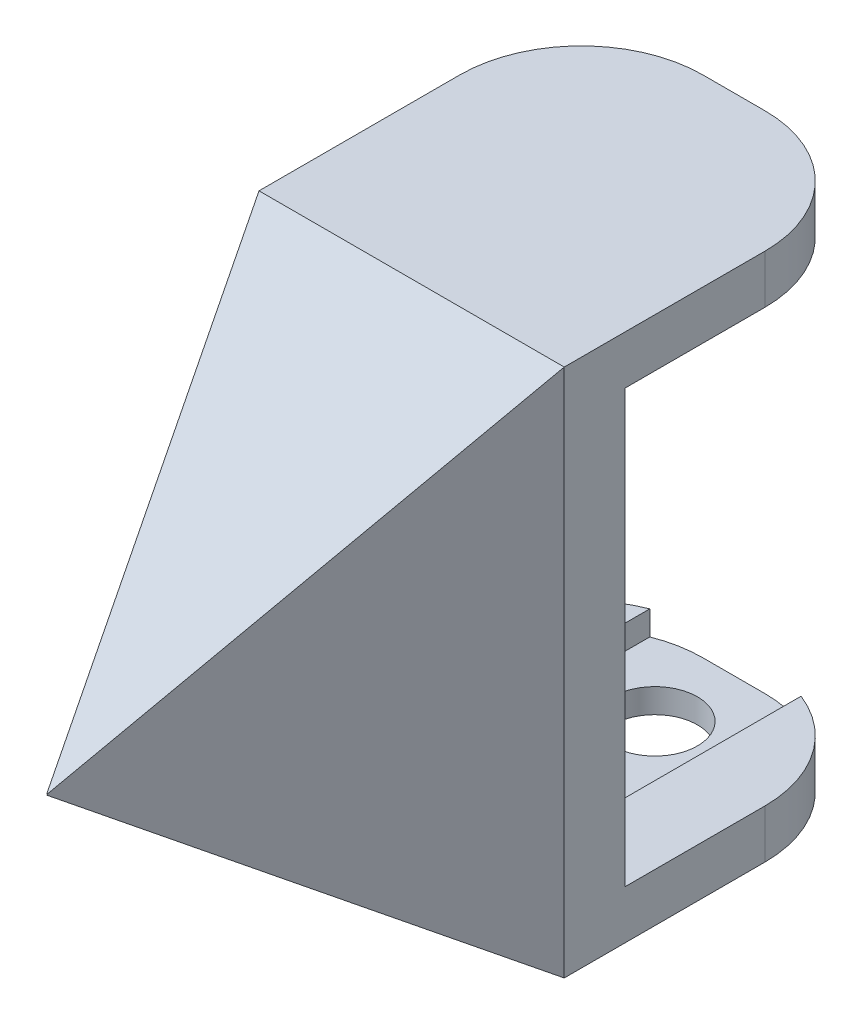
SolidWorks part; units mm, degrees
ref_plane "Front Plane" through (0, 0, 0) normal (0, 0, 1) x (1, 0, 0)
ref_plane "Top Plane" through (0, 0, 0) normal (0, 1, 0) x (1, 0, 0)
ref_plane "Right Plane" through (0, 0, 0) normal (1, 0, 0) x (0, 0, -1)
sketch "Sketch4" plane through (0, 0, 0) normal (0, 0, 1) x (1, 0, 0)
  line L1 (-6.23, -9.975) -> (6.23, -9.975)
  line L2 (-6.23, -9.975) -> (-6.23, 7.275)
  line L3 (-6.23, 7.275) -> (6.23, 7.275)
  line L4 (6.23, -9.975) -> (6.23, 7.275)
  point P4 (0, 7.275)
  dimension "D1" = 12.46
  dimension "D2" = 17.25
  dimension "D3" = 9.975
extrude "Boss-Extrude3" add sketch "Sketch4" along normal blind 6
sketch "Sketch8" plane through (0, -9.975, 0) normal (0, -1, 0) x (-1, 0, 0)
  circle A0 centre (0, -23.55) radius 12.5468
  circle A1 centre (0, -23.55) radius 11.15
  dimension "D1" = 22.3
  dimension "D2" = 23.55
extrude "Boss-Extrude6" add sketch "Sketch8" along normal blind 7.3 and the other way up to surface (17.25 mm away) other way up to face at (0, 7.275, 3)
sketch "Sketch5" plane through (0, 7.275, 0) normal (0, 1, 0) x (1, 0, 0)
  line L8 (12.5468, -23.55) -> (12.5468, 0)
  line L9 (12.5468, 0) -> (6.23, 0)
  line L10 (-12.5468, -23.55) -> (-12.5468, 0)
  line L11 (-12.5468, 0) -> (-6.23, 0)
  line L12 (-6.23, 0) -> (-6.23, -29.7)
  line L14 (6.23, -29.7) -> (6.23, 0)
  line L15 (-6.23, -29.7) -> (6.23, -29.7)
  line L16 (6.23, -6) -> (-6.23, -6) construction
  circle A0 centre (0, -23.55) radius 12.5468 construction
  arc A1 (-12.5468, -23.55) -> (12.5468, -23.55) centre (0, -23.55) ccw
  dimension "D1" = 23.7
  dimension "D2" = 23.55
extrude "Boss-Extrude4" add sketch "Sketch5" against normal up to surface (17.25 mm away) up to face at (0, -9.975, 3)
sketch "Sketch6" plane through (0, 7.275, 0) normal (0, 1, 0) x (1, 0, 0)
  line L0 (6.23, -6) -> (-6.23, -6) construction
  line L3 (6.23, -29.7) -> (-6.23, -29.7) construction
  circle A0 centre (0, -3.5) radius 2
  circle A1 centre (0, -32.2) radius 2
  dimension "D1" = 4
  dimension "D3" = 4
  dimension "D2" = 2.5
  dimension "D4" = 2.5
extrude "Cut-Extrude1" cut sketch "Sketch6" against normal blind 5
chamfer "Chamfer1" distance 0.5 angle 60 2 edges at (0, 7.275, 5.5) (0, 7.275, 34.2) first distance on face at (0, 7.275, 5.5)
sketch "Sketch10" plane through (0, 7.275, 0) normal (0, 1, 0) x (1, 0, 0)
  line L1 (-6.23, -6) -> (6.23, -6)
  line L2 (-6.23, -6) -> (-6.23, -29.7)
  line L3 (-6.23, -29.7) -> (6.23, -29.7)
  line L4 (6.23, -6) -> (6.23, -29.7)
extrude "Cut-Extrude3" cut sketch "Sketch10" against normal up to surface (17.25 mm away) up to face at (0, -9.975, 10.3399)
ref_plane "Plane1" through (0, 0, 36.0968) normal (0, 0, 1) x (1, 0, 0)
sketch "Sketch11" plane through (0, 0, 36.0968) normal (0, 0, 1) x (1, 0, 0)
  line L0 (-11.15, -9.975) -> (11.15, -9.975) construction
  line L1 (-2.5, -6.975) -> (2.5, -6.975)
  line L2 (-2.5, -6.975) -> (-2.5, -9.975)
  line L3 (-2.5, -9.975) -> (2.5, -9.975)
  line L4 (2.5, -6.975) -> (2.5, -9.975)
  point P4 (0, -6.975)
  dimension "D1" = 0
  dimension "D2" = 5
  dimension "D3" = 3
extrude "Cut-Extrude4" cut sketch "Sketch11" against normal up to next
sketch "Sketch13" plane through (0, -17.275, 0) normal (0, -1, 0) x (1, 0, 0)
  line L0 (-12.5468, 23.55) -> (-12.5468, 0)
  line L1 (-12.5468, 0) -> (12.5468, 0)
  line L2 (12.5468, 0) -> (12.5468, 23.55)
  arc A0 (-12.5468, 23.55) -> (12.5468, 23.55) centre (0, 23.55) ccw
  point P3 (0, 0)
extrude "Boss-Extrude7" add sketch "Sketch13" against normal up to surface (7.3 mm away) up to face at (0, -9.975, 10.3399)
sketch "Sketch15" plane through (0, 7.275, 0) normal (0, 1, 0) x (1, 0, 0)
  line L0 (-12.5468, 0) -> (12.5468, 0)
  line L1 (12.5468, 0) -> (12.5468, -23.55)
  line L2 (-12.5468, 0) -> (-12.5468, -23.55)
  line L3 (6.23, -6) -> (6.23, -29.7) construction
  line L4 (-6.23, -0.8) -> (6.23, -0.8)
  line L5 (-6.23, -0.8) -> (-6.23, -33.5)
  line L6 (-5.23, -34.5) -> (5.23, -34.5)
  line L7 (6.23, -0.8) -> (6.23, -33.5)
  arc A0 (-12.5468, -23.55) -> (12.5468, -23.55) centre (0, -23.55) ccw
  circle A1 centre (0, -3.5) radius 2 construction
  arc A2 (5.23, -34.5) -> (6.23, -33.5) centre (5.23, -33.5) ccw
  arc A3 (-6.23, -33.5) -> (-5.23, -34.5) centre (-5.23, -33.5) ccw
  point P15 (0, -0.8)
  dimension "D1" = 0.8
  dimension "D3" = 1
  dimension "D2" = 2.7
  dimension "D4" = 0
  dimension "D5" = 34.5
extrude "Boss-Extrude9" add sketch "Sketch15" along normal blind 10
sketch "Sketch17" plane through (-12.5468, 4.7282, 0) normal (1, 0, 0) x (0, -1, 0)
  line L0 (26.4782, 26.5) -> (26.4782, 0)
  line L1 (26.4782, 0) -> (-17.0218, 0)
  line L2 (-17.0218, 0) -> (-17.0218, 26.5)
  line L3 (-17.0218, 26.5) -> (-13.0218, 26.5)
  line L4 (-13.0218, 26.5) -> (-13.0218, 5)
  line L5 (-13.0218, 5) -> (22.4782, 5)
  line L6 (22.4782, 5) -> (22.4782, 26.5)
  line L7 (22.4782, 26.5) -> (26.4782, 26.5)
  point P2 (4.7282, 5)
  point P10 (4.7282, 0)
  dimension "D1" = 4
  dimension "D2" = 35.5
  dimension "D3" = 0
  dimension "D4" = 26.5
  dimension "D5" = 5
extrude "Boss-Extrude10" add sketch "Sketch17" along normal up to surface (25.0936 mm away) up to face at (12.5468, 0, 11.775)
sketch "Sketch18" plane through (0, -17.75, 0) normal (0, 1, 0) x (0, 0, 1)
  line L0 (-26.5, -12.5468) -> (-26.5, 12.5468) construction
  line L1 (-26.5, 6.2191) -> (-5, 6.2191)
  line L2 (-26.5, 6.2191) -> (-26.5, -6.2191)
  line L3 (-26.5, -6.2191) -> (-5, -6.2191)
  line L4 (-5, 6.2191) -> (-5, -6.2191)
  line L5 (-5, -12.5468) -> (-5, 12.5468) construction
  point P6 (-26.5, 0)
  point P7 (-26.5, 0)
  dimension "D1" = 0
extrude "Cut-Extrude5" cut sketch "Sketch18" against normal blind 2
sketch "Sketch19" plane through (0, -19.75, 0) normal (0, 1, 0) x (0, 0, 1)
  line L0 (-26.5, -12.5468) -> (-26.5, 12.5468) construction
  circle A0 centre (-20, 0) radius 3.5
  dimension "D1" = 7
  dimension "D2" = 6.5
extrude "Cut-Extrude6" cut sketch "Sketch19" against normal through all both and the other way through all
fillet "Fillet1" radius 10 4 edges at (12.5468, -19.75, -26.5) (-12.5468, -19.75, -26.5) (-12.5468, 19.75, -26.5) (12.5468, 19.75, -26.5)
ref_plane "Plane2" through (0, 0, 0) normal (1, 0, 0) x (0, 0, -1)
ref_plane "Plane3" through (0, 0, 0) normal (0, -1, 0) x (-1, 0, 0)
sketch "Sketch20" plane through (0, 17.275, 0) normal (0, 1, 0) x (1, 0, 0)
  line L1 (12.5468, 0) -> (-12.5468, 0)
  line L2 (12.5468, 0) -> (12.5468, -36.0968)
  line L3 (12.5468, -36.0968) -> (-12.5468, -36.0968)
  line L4 (-12.5468, 0) -> (-12.5468, -36.0968)
extrude "Cut-Extrude7" cut sketch "Sketch20" against normal through all both and the other way through all
sketch "Sketch21" plane through (0, 21.75, 0) normal (0, 1, 0) x (1, 0, 0)
  line L0 (12.5468, 0) -> (-0.0254, -30)
  line L1 (-0.0254, -30) -> (-12.5468, 0)
  line L2 (-12.5468, 0) -> (12.5468, 0)
  dimension "D1" = 30
extrude "Boss-Extrude11" add sketch "Sketch21" against normal up to vertex (43.5 mm away) up to point (-12.5468, -21.75, 0)
sketch "Sketch22" plane through (0, 0, 0) normal (1, 0, 0) x (0, 0, -1)
  line L13 (0, 21.75) -> (-30, 0.01)
  line L14 (-30, -21.75) -> (-30, 21.75) construction
  line L15 (-30, 0.01) -> (-30, 21.75)
  line L16 (-30, 21.75) -> (0, 21.75)
  line L17 (0, -21.75) -> (-30, -21.75)
  line L18 (-30, -21.75) -> (-30, -0.01)
  line L19 (-30, -0.01) -> (0, -21.75)
  dimension "D1" = 0.02
  dimension "D2" = 0.01
extrude "Cut-Extrude8" cut sketch "Sketch22" against normal through all both and the other way through all
sketch "Sketch23" plane through (0, 0, 0) normal (0, 0, -1) x (-1, 0, 0)
  line L0 (12.5468, 17.75) -> (0, 0)
  line L1 (0, 0) -> (12.5468, -21.75)
  line L2 (12.5468, -21.75) -> (12.5468, 17.75)
extrude "Cut-Extrude9" cut sketch "Sketch23" against normal through all both and the other way through all
sketch "Sketch24" plane through (0, 21.75, 0) normal (0, 1, 0) x (1, 0, 0)
  circle A0 centre (0, 20) radius 6.5
  dimension "D1" = 13
extrude "Boss-Extrude12" add sketch "Sketch24" against normal blind 5
sketch "Sketch25" plane through (0, 16.75, 0) normal (0, -1, 0) x (1, 0, 0)
  circle A0 centre (0, -20) radius 5.85
  dimension "D1" = 11.7
extrude "Boss-Extrude13" add sketch "Sketch25" along normal blind 5
fillet "Fillet2" radius 1 1 edges at (0, 11.75, -25.85)
